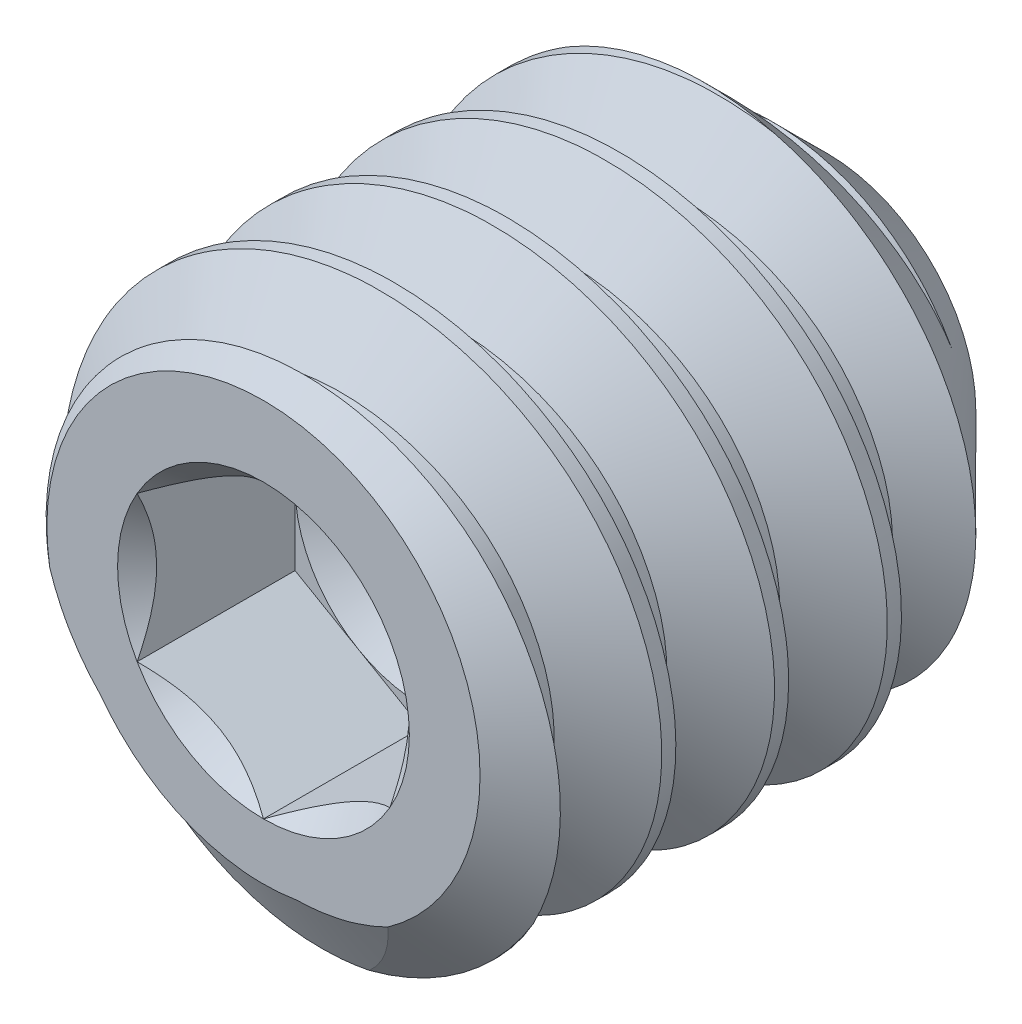
SolidWorks part; units mm, degrees
ref_plane "Front" through (0, 0, 0) normal (0, 0, 1) x (1, 0, 0)
ref_plane "Top" through (0, 0, 0) normal (0, 1, 0) x (1, 0, 0)
ref_plane "Right" through (0, 0, 0) normal (1, 0, 0) x (0, 0, -1)
sketch "Sketch22" plane through (0, 0, 0) normal (1, 0, 0) x (0, 0, -1)
  line L0 (-0.6683, 0) -> (-0.6683, 0.6096)
  line L1 (-0.6683, 0.6096) -> (-0.5616, 0.762)
  line L2 (-0.5616, 0.762) -> (0.5747, 0.762)
  line L3 (0.5747, 0.762) -> (0.9192, 0.4175)
  line L4 (0.9192, 0.4175) -> (0.6683, 0)
  line L5 (0.6683, 0) -> (-0.6683, 0)
  line L6 (0.6683, 0) -> (0.9192, 0) construction
  line L7 (0.9192, 0) -> (0.9192, 0.4175) construction
  line L8 (0.9192, -0.4175) -> (0.6683, 0) construction
  line L9 (-0.5616, -0.762) -> (0.5747, -0.762) construction
  dimension "Dia" = 1.524
  dimension "Length" = 1.5875
  dimension "D3" = 35
  dimension "D5" = 118
  dimension "D6" = 45
  dimension "D7" = 1.2192
revolve "Revolve1" add sketch "Sketch22" angle 360 about L6
ref_plane "Plane1" through (0, 0, -0.9192) normal (0, 0, 1) x (1, 0, 0)
sketch "Sketch27" plane through (0, 0, -0.9192) normal (0, 0, 1) x (1, 0, 0)
  circle A0 centre (0, 0) radius 0.762 construction
  circle A1 centre (0, 0) radius 0.762
curve "Helix/Spiral1" pitch 0.3175 height 2.159 radius 0.762 centre (0, 0, -0.9192) axis (0, 0, 1) start towards (0, 1, 0)
sketch "Sketch28" plane through (0, 0, 0) normal (1, 0, 0) x (0, 0, -1)
  line L0 (0.9192, 0.762) -> (1.197, 0.762)
  line L1 (1.197, 0.762) -> (1.0859, 0.5695)
  line L2 (1.0859, 0.5695) -> (1.0303, 0.5695)
  line L3 (1.0303, 0.5695) -> (0.9192, 0.762)
  line L4 (0.9748, 0.6658) -> (1.1414, 0.6658) construction
  line L6 (-0.5616, 0.762) -> (0.5747, 0.762) construction
  line L7 (0.9192, 0.852) -> (0.9192, -0.852) construction
  dimension "D1" = 0.0556
  dimension "D3" = 60
  dimension "D2" = 0.2778
sweep "Cut-Sweep2" cut profiles "Sketch28" path "Helix/Spiral1" align with end faces yes
sketch "Sketch23" plane through (0, 0, 0.6683) normal (0, 0, 1) x (1, 0, 0)
  line L1 (0, 0.4106) -> (-0.3556, 0.2053)
  line L2 (-0.3556, 0.2053) -> (-0.3556, -0.2053)
  line L3 (-0.3556, -0.2053) -> (0, -0.4106)
  line L4 (0, -0.4106) -> (0.3556, -0.2053)
  line L5 (0.3556, -0.2053) -> (0.3556, 0.2053)
  line L6 (0.3556, 0.2053) -> (0, 0.4106)
  circle A0 centre (0, 0) radius 0.3556 construction
  dimension "Hex" = 0.7112
extrude "Cut-Extrude10" cut sketch "Sketch23" against normal blind 0.4445
sketch "Sketch24" plane through (0, 0, 0.6683) normal (0, 0, 1) x (1, 0, 0)
  circle A0 centre (0, 0) radius 0.4106
extrude "Cut-Extrude11" cut sketch "Sketch24" against normal through all draft 45
sketch "Sketch26" plane through (0, 0, 0.2238) normal (0, 0, 1) x (1, 0, 0)
  circle A0 centre (0, 0) radius 0.3556 construction
  circle A1 centre (0, 0) radius 0.3556
extrude "Cut-Extrude12" cut sketch "Sketch26" against normal through all draft 60
sketch "Sketch30" plane through (0, 0, 0) normal (1, 0, 0) x (0, 0, -1)
  line L0 (-0.5616, 0.762) -> (0.5747, 0.762) construction
  line L1 (-0.6683, 0) -> (-0.6683, 0.6096) construction
  line L2 (0.9192, 0) -> (0.9192, 0.4175) construction
  line L3 (-0.5616, -0.762) -> (0.5747, -0.762) construction
  point P0 (-0.6683, 0.762)
  point P1 (0.9192, 0.762)
  point P2 (0.9192, -0.762)
  point P11 (0.1254, -0.762)
  dimension "D1" = 0.7937
sketch "Sketch31" plane through (0, 0, 0) normal (1, 0, 0) x (0, 0, -1)
  line L2 (0.6683, 0) -> (0.9192, -0.4175)
  line L3 (0.9192, 0.4175) -> (0.6683, 0)
equation "\"D7@Sketch22\"=\"Dia@Sketch22\"*.8"
equation "\"D1@Sketch28\" = \"D4@Helix/Spiral1\" * .175"
equation "\"D3@Helix/Spiral1\" = \"Length@Sketch22\" + \"D4@Helix/Spiral1\" + .01"
equation "\"D1@Sketch30\" = \"D4@Helix/Spiral1\" * 2.5"
equation "\"hex Depth@Cut-Extrude10\" = \"Hex@Sketch23\" * .625"
equation "\"D2@Sketch28\" = \"D4@Helix/Spiral1\" * .875"
